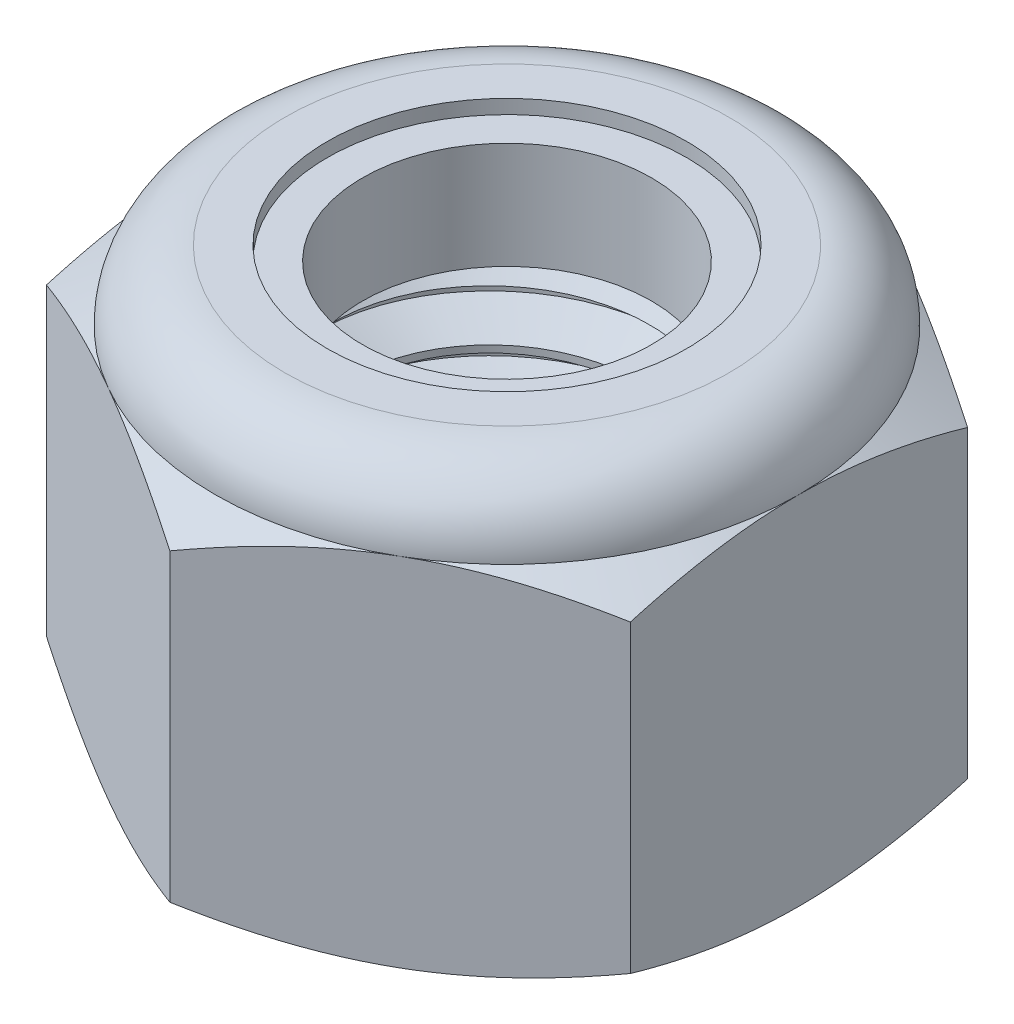
SolidWorks part; units mm, degrees
ref_plane "Front" through (0, 0, 0) normal (0, 0, 1) x (1, 0, 0)
ref_plane "Top" through (0, 0, 0) normal (0, 1, 0) x (1, 0, 0)
ref_plane "Right" through (0, 0, 0) normal (1, 0, 0) x (0, 0, -1)
sketch "Sketch1" plane through (0, 0, 0) normal (0, 1, 0) x (1, 0, 0)
  line L1 (0, 7.5056) -> (-6.5, 3.7528) construction
  line L2 (-6.5, 3.7528) -> (-6.5, -3.7528) construction
  line L3 (-6.5, -3.7528) -> (0, -7.5056) construction
  line L4 (0, -7.5056) -> (6.5, -3.7528) construction
  line L5 (6.5, -3.7528) -> (6.5, 3.7528) construction
  line L6 (6.5, 3.7528) -> (0, 7.5056) construction
  circle A0 centre (0, 0) radius 6.5 construction
  circle A1 centre (0, 0) radius 4 construction
  point P11 (0, -4)
  point P12 (0, 0)
  dimension "Thread Dia" = 8
  dimension "Width" = 13
sketch "Sketch2" plane through (0, 0, 0) normal (1, 0, 0) x (0, 0, -1)
  line L0 (-4, -4.75) -> (-4, 4.75) construction
  line L1 (0, 0) -> (0, 4.75) construction
  line L2 (0, 4.75) -> (-4, 4.75) construction
  line L3 (-4.1353, -4.6719) -> (-3.0528, -5.2969) construction
  line L4 (-3.0528, -5.2969) -> (-4.1353, -5.9219) construction
  line L5 (-4.1353, -5.9219) -> (-4.1353, -4.6719) construction
  line L6 (-3.1881, -5.2187) -> (-3.1881, -5.375) construction
  line L7 (-4.0677, -5.2969) -> (-4.0677, -4.7109) construction
  line L8 (-4, -4.75) -> (-4, -5.8438) construction
  line L9 (-4.1353, -5.2969) -> (-4, -5.2969) construction
  line L10 (-3.1881, -5.2969) -> (-3.0528, -5.2969) construction
  line L11 (-4.0677, -5.2969) -> (-4.0677, -5.8828) construction
  line L12 (-3.2188, 2.0625) -> (-3.2188, 4.4375) construction
  line L13 (-3.2188, 4.4375) -> (-4, 4.4375) construction
  line L14 (-4, 4.4375) -> (-4, 2.0625) construction
  line L15 (-4, 2.0625) -> (-3.2188, 2.0625) construction
  point P6 (-4, 0)
  point P25 (-3.2188, 4.4375)
  dimension "Height" = 9.5
  dimension "Pitch" = 1.25
  dimension "D2" = 0.1562
  dimension "D1" = 0.7812
  dimension "D3" = 2.375
  dimension "D4" = 0.3125
sketch "Sketch3" plane through (0, 0, 0) normal (0, 1, 0) x (1, 0, 0)
  line L0 (0, 7.5056) -> (6.5, 3.7528)
  line L1 (6.5, 3.7528) -> (6.5, -3.7528)
  line L2 (6.5, -3.7528) -> (0, -7.5056)
  line L3 (0, -7.5056) -> (-6.5, -3.7528)
  line L4 (-6.5, -3.7528) -> (-6.5, 3.7528)
  line L5 (-6.5, 3.7528) -> (0, 7.5056)
sketch "Sketch7" plane through (0, 0, 0) normal (0, 1, 0) x (1, 0, 0)
  circle A0 centre (0, 0) radius 6.5 construction
  circle A1 centre (0, 0) radius 6.5
extrude "Boss-Extrude2" add sketch "Sketch3" along normal up to vertex (-4.75 mm away) and the other way up to vertex (4.75 mm away) up to point (0, -4.75, 4) other way up to point (0, -4.75, 4)
sketch "Sketch4" plane through (0, 0, 0) normal (0, 1, 0) x (1, 0, 0)
  circle A0 centre (0, 0) radius 4
  circle A1 centre (0, 0) radius 4 construction
extrude "Cut-Extrude4" cut sketch "Sketch4" along normal through all both and the other way through all
sketch "Sketch6" plane through (0, 0, 0) normal (1, 0, 0) x (0, 0, -1)
  line L0 (6.5, -4.75) -> (6.5, 4.75) construction
  line L7 (6.5, 4.75) -> (6.5, 3.1875) construction
  line L8 (6.5, 4.75) -> (4.9375, 4.75) construction
  line L11 (6.5, 3.1875) -> (7.5056, 3.1875)
  line L13 (7.5056, 3.1875) -> (7.5056, 4.75)
  line L14 (7.5056, 4.75) -> (4.9375, 4.75)
  arc A1 (6.5, 3.1875) -> (4.9375, 4.75) centre (4.9375, 3.1875) ccw
  point P15 (6.5, 0)
  dimension "D1" = 1.5625
revolve "Cut-Revolve1" cut sketch "Sketch6" angle 360 about axis through (0, 4.75, 0) along (0, -1, 0)
extrude "Cut-Extrude5" cut sketch "Sketch7" against normal through all draft 60 from surface flip side to cut starting at face at (0, 3.1875, -6.5449)
sketch "Sketch19" plane through (0, -4.75, 0) normal (0, -1, 0) x (1, 0, 0)
  circle A0 centre (0, 0) radius 6.5 construction
  circle A1 centre (0, 0) radius 6.5
extrude "Cut-Extrude6" cut sketch "Sketch19" against normal through all draft 60 flip side to cut
chamfer "Chamfer1" distance 0.4688 angle 45 1 edges at (0, -4.75, 4)
sketch "Sketch24" plane through (0, 0, 0) normal (1, 0, 0) x (0, 0, -1)
  line L0 (-4, 4.4375) -> (-3.2188, 4.4375)
  line L1 (-3.2188, 4.4375) -> (-3.2188, 2.0625)
  line L2 (-3.2188, 2.0625) -> (-4, 2.0625)
  line L3 (-4, 2.0625) -> (-4, 4.4375)
revolve "Revolve1" add sketch "Sketch24" angle 360 about L1
ref_plane "Contact Plane 1" through (0, 4.75, 0) normal (0, 1, 0) x (1, 0, 0)
ref_plane "Contact Plane 2" through (0, -4.75, 0) normal (0, -1, 0) x (-1, 0, 0)
sketch "Sketch5" plane through (0, -4.75, 0) normal (0, 1, 0) x (1, 0, 0)
  circle A1 centre (0, 0) radius 4
  circle A2 centre (0, 0) radius 4 construction
curve "Helix/Spiral1" pitch 1.25 height 9.5 radius 4 centre (0, -4.75, 0) axis (0, 1, 0) start towards (0, 0, 1)
sketch "Sketch21" plane through (0, 0, 0) normal (1, 0, 0) x (0, 0, -1)
  line L0 (-4.0677, -4.7109) -> (-4.0677, -5.8828)
  line L1 (-4.0677, -5.8828) -> (-3.1881, -5.375)
  line L2 (-3.1881, -5.375) -> (-3.1881, -5.2187)
  line L3 (-3.1881, -5.2187) -> (-4.0677, -4.7109)
sweep "Sweep1" add profiles "Sketch21" path "Helix/Spiral1"
sketch "Sketch23" plane through (0, 2.0625, 0) normal (0, 1, 0) x (1, 0, 0)
  line L0 (0, 0) -> (0, -4) construction
  circle A1 centre (0, 0) radius 4.1353
extrude "Cut-Extrude8" cut sketch "Sketch23" along normal through all and the other way through all draft 45
combine bodies "Combine1" operation type add bodies to combine 147 143
sketch "Sketch30" plane through (0, -4.75, 0) normal (0, -1, 0) x (1, 0, 0)
  circle A0 centre (0, 0) radius 4.4687 construction
  circle A1 centre (0, 0) radius 4.4687
extrude "Cut-Extrude12" cut sketch "Sketch30" along normal through all and the other way through all draft 45
equation "\"D2@Sketch2\" = \"Pitch@Sketch2\" / 8"
equation "\"D1@Sketch2\"=\"Pitch@Sketch2\"*.625"
equation "\"D3@Sketch2\"=\"Height@Sketch2\"/4"
equation "\"D4@Sketch2\"=\"Pitch@Sketch2\"/4"
equation "\"D4@Helix/Spiral1\"=\"Pitch@Sketch2\""
equation "\"D3@Helix/Spiral1\"=\"Height@Sketch2\""
equation "\"D1@Sketch6\"=\"Pitch@Sketch2\"*1.25"
equation "\"D1@Chamfer1\"=\"Pitch@Sketch2\"*.375"
